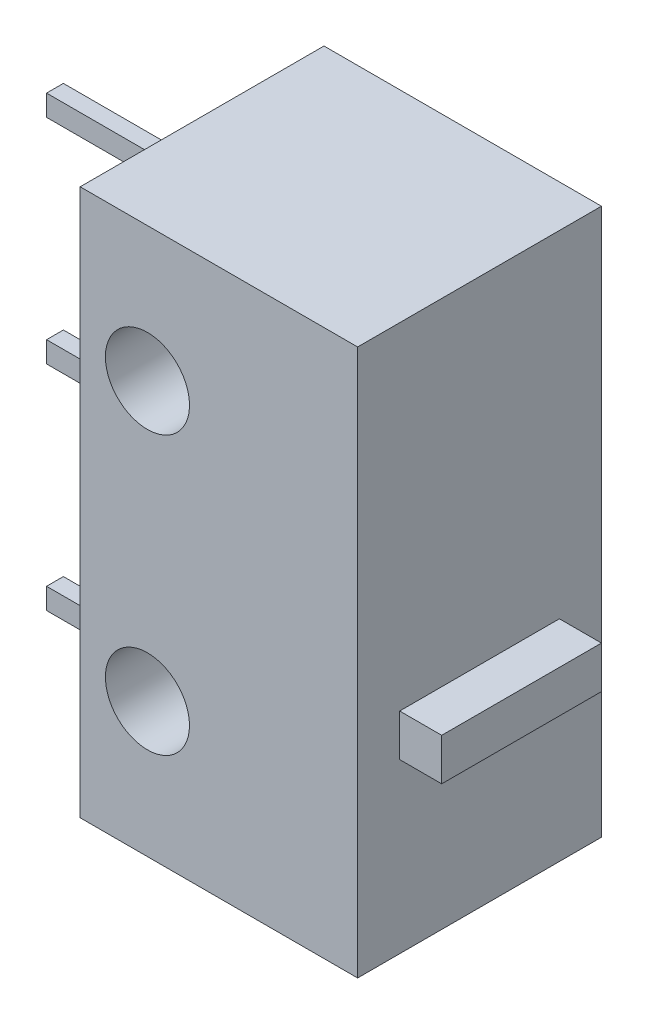
SolidWorks part; units mm, degrees
material "CA"
ref_plane "Front" through (0, 0, 0) normal (0, 0, 1) x (1, 0, 0)
ref_plane "Top" through (0, 0, 0) normal (0, 1, 0) x (1, 0, 0)
ref_plane "Right" through (0, 0, 0) normal (1, 0, 0) x (0, 0, -1)
sketch "Szkic1" plane through (0, 0, 0) normal (0, 0, 1) x (1, 0, 0)
  line L0 (0, 6.5) -> (6.6, 6.5) construction
  line L1 (0, 0) -> (6.6, 0)
  line L2 (0, 0) -> (0, 1.17)
  line L3 (0, 13) -> (6.6, 13)
  line L4 (6.6, 0) -> (6.6, 4)
  line L5 (6.6, 5) -> (6.6, 13)
  line L6 (6.6, 5) -> (7.6, 5)
  line L8 (6.6, 4) -> (7.6, 4)
  line L9 (7.6, 5) -> (7.6, 4)
  line L10 (0, 1.67) -> (-3.5, 1.67)
  line L11 (0, 11.83) -> (-3.5, 11.83)
  line L13 (0, 11.33) -> (-3.5, 11.33)
  line L14 (-3.5, 11.83) -> (-3.5, 11.33)
  line L15 (0, 6.75) -> (-3.5, 6.75)
  line L17 (0, 6.25) -> (-3.5, 6.25)
  line L18 (-3.5, 6.75) -> (-3.5, 6.25)
  line L19 (-3.5, 1.17) -> (-3.5, 1.67)
  line L20 (0, 1.17) -> (-3.5, 1.17)
  line L22 (0, 11.83) -> (0, 13)
  line L23 (0, 6.75) -> (0, 11.33)
  line L24 (0, 1.67) -> (0, 6.25)
  circle A0 centre (1.6, 3.2) radius 1
  circle A1 centre (1.6, 9.8) radius 1
  point P19 (-3.5, 11.58)
  point P24 (-3.5, 6.5)
  dimension "D5" = 2
  dimension "D1" = 6.6
  dimension "D2" = 13
  dimension "D3" = 1.6
  dimension "D4" = 3.2
  dimension "D6" = 1
  dimension "D7" = 1
  dimension "D8" = 4
  dimension "D9" = 3.5
  dimension "D10" = 0.5
  dimension "D11" = 5.08
  dimension "D12" = 0.5
  dimension "D13" = 3.5
  dimension "D14" = 0
extrude "Dodanie-wyciągnięcie1" add sketch "Szkic1" along normal blind 5.8
sketch "Szkic2" plane through (0, 13, 0) normal (0, 1, 0) x (1, 0, 0)
  line L0 (6.6, -5.8) -> (6.6, 0) construction
  line L1 (6.6, -1) -> (7.7487, -1)
  line L2 (6.6, -1) -> (6.6, 0.1983)
  line L3 (6.6, 1.0689) -> (8.4749, 1.0689)
  line L4 (8.4749, -1) -> (8.4749, 1.0689)
  line L5 (7.6, 0) -> (6.6, 0) construction
  line L6 (6.6, -5.8) -> (6.6, 0) construction
  line L7 (6.6, -4.8) -> (7.7487, -4.8)
  line L8 (6.6, -4.8) -> (6.6, -6.1042)
  line L9 (6.6, -6.526) -> (8.4043, -6.526)
  line L10 (8.4043, -4.8) -> (8.4043, -6.526)
  line L11 (7.6, -5.8) -> (6.6, -5.8) construction
  line L12 (7.7487, -1) -> (7.7487, -4.8)
  line L13 (0, 0.6453) -> (6.6, 0.6453)
  line L18 (0, -5.8) -> (0, 0) construction
  line L23 (0, -2.7) -> (-4.3346, -2.7)
  line L24 (0, -2.7) -> (0, -3.1)
  line L25 (0, -3.1) -> (-4.3346, -3.1)
  line L27 (0, -2.7) -> (0, 0.1983)
  line L28 (0, 0.6453) -> (-4.3346, 0.6453)
  line L29 (-4.3346, 0.6453) -> (-4.3346, -2.7)
  line L30 (0, -3.1) -> (0, -6.1042)
  line L31 (0, -6.526) -> (-4.3346, -6.5966)
  line L32 (-4.3346, -6.5966) -> (-4.3346, -3.1)
  line L33 (0, -3.1) -> (-4.3346, -3.1)
  line L34 (-4.3346, -2.7) -> (-4.3346, -3.1)
  line L35 (0, 0.1983) -> (6.6, 0.1983)
  line L36 (6.6, 0.6453) -> (6.6, 1.0689)
  line L37 (0, -6.526) -> (6.6, -6.526)
  line L38 (0, -6.1042) -> (6.6, -6.1042)
  line L39 (8.4043, -4.8) -> (8.4043, -1)
  line L40 (8.4043, -1) -> (8.4749, -1)
  line M18 (0, 0) -> (0, -5.8)
  line M20 (6.6, -5.8) -> (6.6, 0)
  dimension "D1" = 1
  dimension "D2" = 1
  dimension "D4" = 0.4
extrude "Wytnij-wyciągnięcie1" cut sketch "Szkic2" against normal through all contours L39 L40 L4 L3 L36 L13 L28 L29 L23 L27 L35 L2 L1 L12 L7 L8 L38 L30 L25 L32 L31 L37 L9 L10 M18 M20 region at (6.7493, 13, 0.5)
